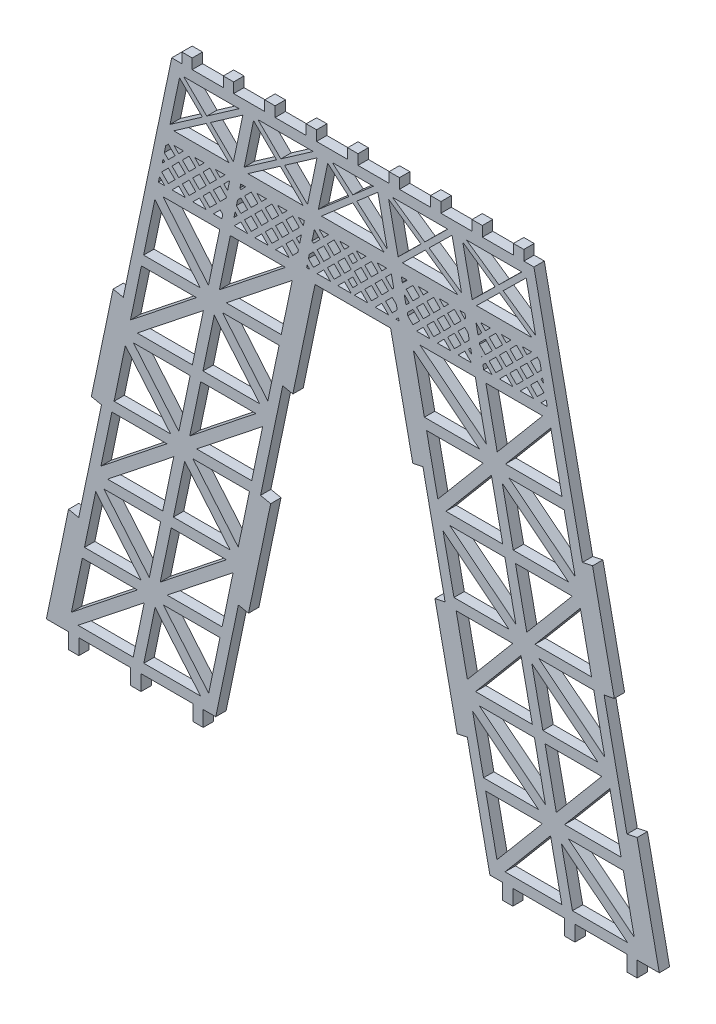
SolidWorks part; units mm, degrees
ref_plane "Front Plane" through (0, 0, 0) normal (0, 0, 1) x (1, 0, 0)
ref_plane "Top Plane" through (0, 0, 0) normal (0, 1, 0) x (1, 0, 0)
ref_plane "Right Plane" through (0, 0, 0) normal (1, 0, 0) x (0, 0, -1)
sketch "Sketch1" plane through (0, 0, 0) normal (0, 0, 1) x (1, 0, 0)
  line L1727 (344.6041, 258) -> (328.6274, 258)
  line L1728 (328.6274, 258) -> (347.7842, 242.7952)
  line L1729 (347.7842, 242.7952) -> (344.6041, 258)
  line L1730 (329.8663, 240.5406) -> (345.7992, 240.5406)
  line L1731 (345.7992, 240.5406) -> (326.6949, 255.7038)
  line L1732 (326.6949, 255.7038) -> (329.8663, 240.5406)
  line L1733 (354.4046, 237.5406) -> (370.3376, 237.5406)
  line L1734 (370.3376, 237.5406) -> (373.509, 222.3774)
  line L1735 (373.509, 222.3774) -> (354.4046, 237.5406)
  line L1736 (352.4197, 235.286) -> (355.5998, 220.0812)
  line L1737 (355.5998, 220.0812) -> (371.5764, 220.0812)
  line L1738 (371.5764, 220.0812) -> (352.4197, 235.286)
  line L1739 (353.1623, 217.0812) -> (337.1856, 217.0812)
  line L1740 (337.1856, 217.0812) -> (356.3424, 201.8765)
  line L1741 (356.3424, 201.8765) -> (353.1623, 217.0812)
  line L1742 (338.4245, 199.6218) -> (354.3574, 199.6218)
  line L1743 (354.3574, 199.6218) -> (335.2531, 214.785)
  line L1744 (335.2531, 214.785) -> (338.4245, 199.6218)
  line L1745 (362.9628, 196.6218) -> (378.8958, 196.6218)
  line L1746 (378.8958, 196.6218) -> (382.0672, 181.4586)
  line L1747 (382.0672, 181.4586) -> (362.9628, 196.6218)
  line L1748 (360.9779, 194.3672) -> (364.158, 179.1624)
  line L1749 (364.158, 179.1624) -> (380.1346, 179.1624)
  line L1750 (380.1346, 179.1624) -> (360.9779, 194.3672)
  line L1751 (361.7205, 176.1624) -> (345.7438, 176.1624)
  line L1752 (345.7438, 176.1624) -> (364.9006, 160.9577)
  line L1753 (364.9006, 160.9577) -> (361.7205, 176.1624)
  line L1754 (346.9827, 158.703) -> (362.9157, 158.703)
  line L1755 (362.9157, 158.703) -> (343.8113, 173.8662)
  line L1756 (343.8113, 173.8662) -> (346.9827, 158.703)
  line L1757 (371.521, 155.703) -> (387.454, 155.703)
  line L1758 (387.454, 155.703) -> (390.6254, 140.5398)
  line L1759 (390.6254, 140.5398) -> (371.521, 155.703)
  line L1760 (369.5361, 153.4484) -> (372.7162, 138.2436)
  line L1761 (372.7162, 138.2436) -> (388.6929, 138.2436)
  line L1762 (388.6929, 138.2436) -> (369.5361, 153.4484)
  line L1763 (369.6513, 138.2436) -> (366.3812, 153.8788)
  line L1764 (366.3812, 153.8788) -> (353.2223, 138.2436)
  line L1765 (353.2223, 138.2436) -> (369.6513, 138.2436)
  line L1766 (363.9954, 155.703) -> (350.8716, 140.1094)
  line L1767 (350.8716, 140.1094) -> (347.6101, 155.703)
  line L1768 (347.6101, 155.703) -> (363.9954, 155.703)
  line L1769 (364.7854, 176.1624) -> (368.0555, 160.5272)
  line L1770 (368.0555, 160.5272) -> (381.2144, 176.1624)
  line L1771 (381.2144, 176.1624) -> (364.7854, 176.1624)
  line L1772 (370.4413, 158.703) -> (383.5651, 174.2966)
  line L1773 (383.5651, 174.2966) -> (386.8266, 158.703)
  line L1774 (386.8266, 158.703) -> (370.4413, 158.703)
  line L1775 (361.0931, 179.1624) -> (357.8229, 194.7976)
  line L1776 (357.8229, 194.7976) -> (344.6641, 179.1624)
  line L1777 (344.6641, 179.1624) -> (361.0931, 179.1624)
  line L1778 (355.4372, 196.6218) -> (339.0519, 196.6218)
  line L1779 (339.0519, 196.6218) -> (342.3133, 181.0282)
  line L1780 (342.3133, 181.0282) -> (355.4372, 196.6218)
  line L1781 (356.2272, 217.0812) -> (359.4973, 201.446)
  line L1782 (359.4973, 201.446) -> (372.6562, 217.0812)
  line L1783 (372.6562, 217.0812) -> (356.2272, 217.0812)
  line L1784 (361.8831, 199.6218) -> (375.0069, 215.2154)
  line L1785 (375.0069, 215.2154) -> (378.2684, 199.6218)
  line L1786 (378.2684, 199.6218) -> (361.8831, 199.6218)
  line L1787 (352.5348, 220.0812) -> (349.2647, 235.7164)
  line L1788 (349.2647, 235.7164) -> (336.1059, 220.0812)
  line L1789 (336.1059, 220.0812) -> (352.5348, 220.0812)
  line L1790 (346.879, 237.5406) -> (330.4937, 237.5406)
  line L1791 (330.4937, 237.5406) -> (333.7551, 221.947)
  line L1792 (333.7551, 221.947) -> (346.879, 237.5406)
  line L1793 (347.669, 258) -> (350.9391, 242.3648)
  line L1794 (350.9391, 242.3648) -> (364.0979, 258)
  line L1795 (364.0979, 258) -> (347.669, 258)
  line L1796 (353.3249, 240.5406) -> (366.4487, 256.1342)
  line L1797 (366.4487, 256.1342) -> (369.7101, 240.5406)
  line L1798 (369.7101, 240.5406) -> (353.3249, 240.5406)
  line L1799 (340.9768, 289.9971) -> (343.7077, 276.9397)
  line L1800 (343.7077, 276.9397) -> (350.3463, 283.4684)
  line L1801 (350.3463, 283.4684) -> (340.9768, 289.9971)
  line L1802 (352.6864, 283.666) -> (362.0559, 277.1373)
  line L1803 (362.0559, 277.1373) -> (359.3249, 290.1947)
  line L1804 (359.3249, 290.1947) -> (352.6864, 283.666)
  line L1805 (360.9678, 276.0672) -> (351.5983, 282.5959)
  line L1806 (351.5983, 282.5959) -> (344.9598, 276.0672)
  line L1807 (344.9598, 276.0672) -> (360.9678, 276.0672)
  line L1808 (342.0648, 291.0672) -> (351.4343, 284.5385)
  line L1809 (351.4343, 284.5385) -> (358.0728, 291.0672)
  line L1810 (358.0728, 291.0672) -> (342.0648, 291.0672)
  line L1811 (340.6015, 277.1373) -> (337.8705, 290.1947)
  line L1812 (337.8705, 290.1947) -> (331.232, 283.666)
  line L1813 (331.232, 283.666) -> (340.6015, 277.1373)
  line L1814 (339.5134, 276.0672) -> (330.144, 282.5959)
  line L1815 (330.144, 282.5959) -> (323.5054, 276.0672)
  line L1816 (323.5054, 276.0672) -> (339.5134, 276.0672)
  line L1817 (319.5224, 289.9971) -> (322.2534, 276.9397)
  line L1818 (322.2534, 276.9397) -> (328.8919, 283.4684)
  line L1819 (328.8919, 283.4684) -> (319.5224, 289.9971)
  line L1820 (320.6104, 291.0672) -> (329.9799, 284.5385)
  line L1821 (329.9799, 284.5385) -> (336.6184, 291.0672)
  line L1822 (336.6184, 291.0672) -> (320.6104, 291.0672)
  line L1823 (319.1174, 277.2791) -> (316.4094, 290.2271)
  line L1824 (316.4094, 290.2271) -> (310.2902, 284.9261)
  line L1825 (310.2902, 284.9261) -> (319.1174, 277.2791)
  line L1826 (316.1711, 272.4369) -> (317.5474, 271.0607)
  line L1827 (317.5474, 271.0607) -> (318.9237, 272.4369)
  line L1828 (318.9237, 272.4369) -> (316.1711, 272.4369)
  line L1829 (310.1711, 272.4369) -> (311.5474, 271.0607)
  line L1830 (311.5474, 271.0607) -> (312.9237, 272.4369)
  line L1831 (312.9237, 272.4369) -> (310.1711, 272.4369)
  line L1832 (309.6081, 267) -> (311.5474, 265.0607)
  line L1833 (311.5474, 265.0607) -> (313.4868, 267)
  line L1834 (313.4868, 267) -> (311.5474, 268.9393)
  line L1835 (311.5474, 268.9393) -> (309.6081, 267)
  line L1836 (314.5474, 268.0607) -> (316.4868, 270)
  line L1837 (316.4868, 270) -> (314.5474, 271.9393)
  line L1838 (314.5474, 271.9393) -> (312.6081, 270)
  line L1839 (312.6081, 270) -> (314.5474, 268.0607)
  line L1840 (311.5474, 262.9393) -> (309.6081, 261)
  line L1841 (309.6081, 261) -> (313.4868, 261)
  line L1842 (313.4868, 261) -> (311.5474, 262.9393)
  line L1843 (314.5474, 265.9393) -> (312.6081, 264)
  line L1844 (312.6081, 264) -> (314.5474, 262.0607)
  line L1845 (314.5474, 262.0607) -> (316.4868, 264)
  line L1846 (316.4868, 264) -> (314.5474, 265.9393)
  line L1847 (317.5474, 268.9393) -> (315.6081, 267)
  line L1848 (315.6081, 267) -> (317.5474, 265.0607)
  line L1849 (317.5474, 265.0607) -> (319.4868, 267)
  line L1850 (319.4868, 267) -> (317.5474, 268.9393)
  line L1851 (323.1951, 272.4369) -> (323.4659, 271.1422)
  line L1852 (323.4659, 271.1422) -> (323.5474, 271.0607)
  line L1853 (323.5474, 271.0607) -> (324.9237, 272.4369)
  line L1854 (324.9237, 272.4369) -> (323.1951, 272.4369)
  line L1855 (320.2884, 271.6803) -> (318.6081, 270)
  line L1856 (318.6081, 270) -> (320.5474, 268.0607)
  line L1857 (320.5474, 268.0607) -> (320.9593, 268.4726)
  line L1858 (320.9593, 268.4726) -> (320.2884, 271.6803)
  line L1859 (322.5222, 261) -> (322.3641, 261.756)
  line L1860 (322.3641, 261.756) -> (321.6081, 261)
  line L1861 (321.6081, 261) -> (322.5222, 261)
  line L1862 (317.5474, 262.9393) -> (315.6081, 261)
  line L1863 (315.6081, 261) -> (319.4868, 261)
  line L1864 (319.4868, 261) -> (317.5474, 262.9393)
  line L1865 (321.7382, 264.7485) -> (320.5474, 265.9393)
  line L1866 (320.5474, 265.9393) -> (318.6081, 264)
  line L1867 (318.6081, 264) -> (320.5474, 262.0607)
  line L1868 (320.5474, 262.0607) -> (321.9972, 263.5104)
  line L1869 (321.9972, 263.5104) -> (321.7382, 264.7485)
  line L1870 (324.0269, 268.4598) -> (324.5319, 266.0452)
  line L1871 (324.5319, 266.0452) -> (325.4868, 267)
  line L1872 (325.4868, 267) -> (324.0269, 268.4598)
  line L1873 (326.5474, 271.9393) -> (324.6081, 270)
  line L1874 (324.6081, 270) -> (326.5474, 268.0607)
  line L1875 (326.5474, 268.0607) -> (328.4868, 270)
  line L1876 (328.4868, 270) -> (326.5474, 271.9393)
  line L1877 (328.1711, 272.4369) -> (329.5474, 271.0607)
  line L1878 (329.5474, 271.0607) -> (330.9237, 272.4369)
  line L1879 (330.9237, 272.4369) -> (328.1711, 272.4369)
  line L1880 (326.5474, 265.9393) -> (324.8989, 264.2908)
  line L1881 (324.8989, 264.2908) -> (325.0527, 263.5554)
  line L1882 (325.0527, 263.5554) -> (326.5474, 262.0607)
  line L1883 (326.5474, 262.0607) -> (328.4868, 264)
  line L1884 (328.4868, 264) -> (326.5474, 265.9393)
  line L1885 (329.5474, 268.9393) -> (327.6081, 267)
  line L1886 (327.6081, 267) -> (329.5474, 265.0607)
  line L1887 (329.5474, 265.0607) -> (331.4868, 267)
  line L1888 (331.4868, 267) -> (329.5474, 268.9393)
  line L1889 (332.5474, 271.9393) -> (330.6081, 270)
  line L1890 (330.6081, 270) -> (332.5474, 268.0607)
  line L1891 (332.5474, 268.0607) -> (334.4868, 270)
  line L1892 (334.4868, 270) -> (332.5474, 271.9393)
  line L1893 (334.1711, 272.4369) -> (335.5474, 271.0607)
  line L1894 (335.5474, 271.0607) -> (336.9237, 272.4369)
  line L1895 (336.9237, 272.4369) -> (334.1711, 272.4369)
  line L1896 (329.5474, 262.9393) -> (327.6081, 261)
  line L1897 (327.6081, 261) -> (331.4868, 261)
  line L1898 (331.4868, 261) -> (329.5474, 262.9393)
  line L1899 (332.5474, 265.9393) -> (330.6081, 264)
  line L1900 (330.6081, 264) -> (332.5474, 262.0607)
  line L1901 (332.5474, 262.0607) -> (334.4868, 264)
  line L1902 (334.4868, 264) -> (332.5474, 265.9393)
  line L1903 (335.5474, 268.9393) -> (333.6081, 267)
  line L1904 (333.6081, 267) -> (335.5474, 265.0607)
  line L1905 (335.5474, 265.0607) -> (337.4868, 267)
  line L1906 (337.4868, 267) -> (335.5474, 268.9393)
  line L1907 (338.5474, 271.9393) -> (336.6081, 270)
  line L1908 (336.6081, 270) -> (338.5474, 268.0607)
  line L1909 (338.5474, 268.0607) -> (340.4868, 270)
  line L1910 (340.4868, 270) -> (338.5474, 271.9393)
  line L1911 (341.5846, 272.4369) -> (340.1711, 272.4369)
  line L1912 (340.1711, 272.4369) -> (341.5474, 271.0607)
  line L1913 (341.5474, 271.0607) -> (341.8162, 271.3295)
  line L1914 (341.8162, 271.3295) -> (341.5846, 272.4369)
  line L1915 (343.5452, 263.0629) -> (343.221, 264.6129)
  line L1916 (343.221, 264.6129) -> (342.6081, 264)
  line L1917 (342.6081, 264) -> (343.5452, 263.0629)
  line L1918 (335.5474, 262.9393) -> (333.6081, 261)
  line L1919 (333.6081, 261) -> (337.4868, 261)
  line L1920 (337.4868, 261) -> (335.5474, 262.9393)
  line L1921 (338.5474, 265.9393) -> (336.6081, 264)
  line L1922 (336.6081, 264) -> (338.5474, 262.0607)
  line L1923 (338.5474, 262.0607) -> (340.4868, 264)
  line L1924 (340.4868, 264) -> (338.5474, 265.9393)
  line L1925 (342.5194, 267.9674) -> (341.5474, 268.9393)
  line L1926 (341.5474, 268.9393) -> (339.6081, 267)
  line L1927 (339.6081, 267) -> (341.5474, 265.0607)
  line L1928 (341.5474, 265.0607) -> (342.8541, 266.3673)
  line L1929 (342.8541, 266.3673) -> (342.5194, 267.9674)
  line L1930 (344.8081, 271.6787) -> (345.3888, 268.9021)
  line L1931 (345.3888, 268.9021) -> (346.4868, 270)
  line L1932 (346.4868, 270) -> (344.8081, 271.6787)
  line L1933 (346.1711, 272.4369) -> (347.5474, 271.0607)
  line L1934 (347.5474, 271.0607) -> (348.9237, 272.4369)
  line L1935 (348.9237, 272.4369) -> (346.1711, 272.4369)
  line L1936 (341.5474, 262.9393) -> (339.6081, 261)
  line L1937 (339.6081, 261) -> (343.4868, 261)
  line L1938 (343.4868, 261) -> (341.5474, 262.9393)
  line L1939 (346.3949, 264.0919) -> (346.4267, 263.9399)
  line L1940 (346.4267, 263.9399) -> (346.4868, 264)
  line L1941 (346.4868, 264) -> (346.3949, 264.0919)
  line L1942 (347.5474, 268.9393) -> (345.7558, 267.1477)
  line L1943 (345.7558, 267.1477) -> (345.8339, 266.7742)
  line L1944 (345.8339, 266.7742) -> (347.5474, 265.0607)
  line L1945 (347.5474, 265.0607) -> (349.4868, 267)
  line L1946 (349.4868, 267) -> (347.5474, 268.9393)
  line L1947 (350.5474, 271.9393) -> (348.6081, 270)
  line L1948 (348.6081, 270) -> (350.5474, 268.0607)
  line L1949 (350.5474, 268.0607) -> (352.4868, 270)
  line L1950 (352.4868, 270) -> (350.5474, 271.9393)
  line L1951 (352.1711, 272.4369) -> (353.5474, 271.0607)
  line L1952 (353.5474, 271.0607) -> (354.9237, 272.4369)
  line L1953 (354.9237, 272.4369) -> (352.1711, 272.4369)
  line L1954 (347.5474, 262.9393) -> (346.7936, 262.1855)
  line L1955 (346.7936, 262.1855) -> (347.0415, 261)
  line L1956 (347.0415, 261) -> (349.4868, 261)
  line L1957 (349.4868, 261) -> (347.5474, 262.9393)
  line L1958 (350.5474, 265.9393) -> (348.6081, 264)
  line L1959 (348.6081, 264) -> (350.5474, 262.0607)
  line L1960 (350.5474, 262.0607) -> (352.4868, 264)
  line L1961 (352.4868, 264) -> (350.5474, 265.9393)
  line L1962 (353.5474, 268.9393) -> (351.6081, 267)
  line L1963 (351.6081, 267) -> (353.5474, 265.0607)
  line L1964 (353.5474, 265.0607) -> (355.4868, 267)
  line L1965 (355.4868, 267) -> (353.5474, 268.9393)
  line L1966 (356.5474, 271.9393) -> (354.6081, 270)
  line L1967 (354.6081, 270) -> (356.5474, 268.0607)
  line L1968 (356.5474, 268.0607) -> (358.4868, 270)
  line L1969 (358.4868, 270) -> (356.5474, 271.9393)
  line L1970 (358.1711, 272.4369) -> (359.5474, 271.0607)
  line L1971 (359.5474, 271.0607) -> (360.9237, 272.4369)
  line L1972 (360.9237, 272.4369) -> (358.1711, 272.4369)
  line L1973 (353.5474, 262.9393) -> (351.6081, 261)
  line L1974 (351.6081, 261) -> (355.4868, 261)
  line L1975 (355.4868, 261) -> (353.5474, 262.9393)
  line L1976 (356.5474, 265.9393) -> (354.6081, 264)
  line L1977 (354.6081, 264) -> (356.5474, 262.0607)
  line L1978 (356.5474, 262.0607) -> (358.4868, 264)
  line L1979 (358.4868, 264) -> (356.5474, 265.9393)
  line L1980 (359.5474, 268.9393) -> (357.6081, 267)
  line L1981 (357.6081, 267) -> (359.5474, 265.0607)
  line L1982 (359.5474, 265.0607) -> (361.4868, 267)
  line L1983 (361.4868, 267) -> (359.5474, 268.9393)
  line L1984 (363.3006, 271.1862) -> (362.5474, 271.9393)
  line L1985 (362.5474, 271.9393) -> (360.6081, 270)
  line L1986 (360.6081, 270) -> (362.5474, 268.0607)
  line L1987 (362.5474, 268.0607) -> (363.7109, 269.2242)
  line L1988 (363.7109, 269.2242) -> (363.3006, 271.1862)
  line L1989 (363.6081, 267) -> (364.3263, 266.2817)
  line L1990 (364.3263, 266.2817) -> (364.0779, 267.4698)
  line L1991 (364.0779, 267.4698) -> (363.6081, 267)
  line L1992 (359.5474, 262.9393) -> (357.6081, 261)
  line L1993 (357.6081, 261) -> (361.4868, 261)
  line L1994 (361.4868, 261) -> (359.5474, 262.9393)
  line L1995 (362.5474, 265.9393) -> (360.6081, 264)
  line L1996 (360.6081, 264) -> (362.5474, 262.0607)
  line L1997 (362.5474, 262.0607) -> (364.4868, 264)
  line L1998 (364.4868, 264) -> (362.5474, 265.9393)
  line L1999 (365.1157, 262.5076) -> (365.431, 261)
  line L2000 (365.431, 261) -> (363.6081, 261)
  line L2001 (363.6081, 261) -> (365.1157, 262.5076)
  line L2002 (273.6855, 258) -> (289.6622, 258)
  line L2003 (289.6622, 258) -> (270.5055, 242.7952)
  line L2004 (270.5055, 242.7952) -> (273.6855, 258)
  line L2005 (288.4234, 240.5406) -> (272.4904, 240.5406)
  line L2006 (272.4904, 240.5406) -> (291.5948, 255.7038)
  line L2007 (291.5948, 255.7038) -> (288.4234, 240.5406)
  line L2008 (244.7807, 222.3774) -> (247.952, 237.5406)
  line L2009 (247.952, 237.5406) -> (263.885, 237.5406)
  line L2010 (263.885, 237.5406) -> (244.7807, 222.3774)
  line L2011 (265.87, 235.286) -> (262.6899, 220.0812)
  line L2012 (262.6899, 220.0812) -> (246.7132, 220.0812)
  line L2013 (246.7132, 220.0812) -> (265.87, 235.286)
  line L2014 (265.1273, 217.0812) -> (281.104, 217.0812)
  line L2015 (281.104, 217.0812) -> (261.9472, 201.8765)
  line L2016 (261.9472, 201.8765) -> (265.1273, 217.0812)
  line L2017 (279.8652, 199.6218) -> (263.9322, 199.6218)
  line L2018 (263.9322, 199.6218) -> (283.0366, 214.785)
  line L2019 (283.0366, 214.785) -> (279.8652, 199.6218)
  line L2020 (236.2224, 181.4586) -> (239.3938, 196.6218)
  line L2021 (239.3938, 196.6218) -> (255.3268, 196.6218)
  line L2022 (255.3268, 196.6218) -> (236.2224, 181.4586)
  line L2023 (257.3118, 194.3672) -> (254.1317, 179.1624)
  line L2024 (254.1317, 179.1624) -> (238.155, 179.1624)
  line L2025 (238.155, 179.1624) -> (257.3118, 194.3672)
  line L2026 (256.5691, 176.1624) -> (272.5458, 176.1624)
  line L2027 (272.5458, 176.1624) -> (253.389, 160.9577)
  line L2028 (253.389, 160.9577) -> (256.5691, 176.1624)
  line L2029 (271.307, 158.703) -> (255.374, 158.703)
  line L2030 (255.374, 158.703) -> (274.4783, 173.8662)
  line L2031 (274.4783, 173.8662) -> (271.307, 158.703)
  line L2032 (227.6642, 140.5398) -> (230.8356, 155.703)
  line L2033 (230.8356, 155.703) -> (246.7686, 155.703)
  line L2034 (246.7686, 155.703) -> (227.6642, 140.5398)
  line L2035 (229.5968, 138.2436) -> (245.5734, 138.2436)
  line L2036 (245.5734, 138.2436) -> (248.7535, 153.4484)
  line L2037 (248.7535, 153.4484) -> (229.5968, 138.2436)
  line L2038 (248.6384, 138.2436) -> (251.9085, 153.8788)
  line L2039 (251.9085, 153.8788) -> (265.0673, 138.2436)
  line L2040 (265.0673, 138.2436) -> (248.6384, 138.2436)
  line L2041 (270.6795, 155.703) -> (267.4181, 140.1094)
  line L2042 (267.4181, 140.1094) -> (254.2943, 155.703)
  line L2043 (254.2943, 155.703) -> (270.6795, 155.703)
  line L2044 (253.5042, 176.1624) -> (250.2341, 160.5272)
  line L2045 (250.2341, 160.5272) -> (237.0753, 176.1624)
  line L2046 (237.0753, 176.1624) -> (253.5042, 176.1624)
  line L2047 (231.4631, 158.703) -> (234.7245, 174.2966)
  line L2048 (234.7245, 174.2966) -> (247.8483, 158.703)
  line L2049 (247.8483, 158.703) -> (231.4631, 158.703)
  line L2050 (257.1966, 179.1624) -> (260.4667, 194.7976)
  line L2051 (260.4667, 194.7976) -> (273.6255, 179.1624)
  line L2052 (273.6255, 179.1624) -> (257.1966, 179.1624)
  line L2053 (275.9763, 181.0282) -> (279.2377, 196.6218)
  line L2054 (279.2377, 196.6218) -> (262.8525, 196.6218)
  line L2055 (262.8525, 196.6218) -> (275.9763, 181.0282)
  line L2056 (262.0624, 217.0812) -> (258.7923, 201.446)
  line L2057 (258.7923, 201.446) -> (245.6335, 217.0812)
  line L2058 (245.6335, 217.0812) -> (262.0624, 217.0812)
  line L2059 (240.0213, 199.6218) -> (243.2827, 215.2154)
  line L2060 (243.2827, 215.2154) -> (256.4065, 199.6218)
  line L2061 (256.4065, 199.6218) -> (240.0213, 199.6218)
  line L2062 (265.7548, 220.0812) -> (269.0249, 235.7164)
  line L2063 (269.0249, 235.7164) -> (282.1837, 220.0812)
  line L2064 (282.1837, 220.0812) -> (265.7548, 220.0812)
  line L2065 (284.5345, 221.947) -> (287.7959, 237.5406)
  line L2066 (287.7959, 237.5406) -> (271.4107, 237.5406)
  line L2067 (271.4107, 237.5406) -> (284.5345, 221.947)
  line L2068 (270.6206, 258) -> (267.3505, 242.3648)
  line L2069 (267.3505, 242.3648) -> (254.1917, 258)
  line L2070 (254.1917, 258) -> (270.6206, 258)
  line L2071 (248.5795, 240.5406) -> (251.8409, 256.1342)
  line L2072 (251.8409, 256.1342) -> (264.9647, 240.5406)
  line L2073 (264.9647, 240.5406) -> (248.5795, 240.5406)
  line L2074 (277.3129, 289.9971) -> (274.5819, 276.9397)
  line L2075 (274.5819, 276.9397) -> (267.9434, 283.4684)
  line L2076 (267.9434, 283.4684) -> (277.3129, 289.9971)
  line L2077 (258.9647, 290.1947) -> (256.2337, 277.1373)
  line L2078 (256.2337, 277.1373) -> (265.6032, 283.666)
  line L2079 (265.6032, 283.666) -> (258.9647, 290.1947)
  line L2080 (257.3218, 276.0672) -> (266.6913, 282.5959)
  line L2081 (266.6913, 282.5959) -> (273.3298, 276.0672)
  line L2082 (273.3298, 276.0672) -> (257.3218, 276.0672)
  line L2083 (276.2248, 291.0672) -> (266.8553, 284.5385)
  line L2084 (266.8553, 284.5385) -> (260.2168, 291.0672)
  line L2085 (260.2168, 291.0672) -> (276.2248, 291.0672)
  line L2086 (277.6881, 277.1373) -> (280.4191, 290.1947)
  line L2087 (280.4191, 290.1947) -> (287.0576, 283.666)
  line L2088 (287.0576, 283.666) -> (277.6881, 277.1373)
  line L2089 (278.7762, 276.0672) -> (288.1457, 282.5959)
  line L2090 (288.1457, 282.5959) -> (294.7842, 276.0672)
  line L2091 (294.7842, 276.0672) -> (278.7762, 276.0672)
  line L2092 (298.7673, 289.9971) -> (296.0363, 276.9397)
  line L2093 (296.0363, 276.9397) -> (289.3978, 283.4684)
  line L2094 (289.3978, 283.4684) -> (298.7673, 289.9971)
  line L2095 (297.6792, 291.0672) -> (288.3097, 284.5385)
  line L2096 (288.3097, 284.5385) -> (281.6712, 291.0672)
  line L2097 (281.6712, 291.0672) -> (297.6792, 291.0672)
  line L2098 (299.1722, 277.2791) -> (301.8803, 290.2271)
  line L2099 (301.8803, 290.2271) -> (307.9994, 284.9261)
  line L2100 (307.9994, 284.9261) -> (299.1722, 277.2791)
  line L2101 (302.1185, 272.4369) -> (300.7422, 271.0607)
  line L2102 (300.7422, 271.0607) -> (299.3659, 272.4369)
  line L2103 (299.3659, 272.4369) -> (302.1185, 272.4369)
  line L2104 (308.1185, 272.4369) -> (306.7422, 271.0607)
  line L2105 (306.7422, 271.0607) -> (305.3659, 272.4369)
  line L2106 (305.3659, 272.4369) -> (308.1185, 272.4369)
  line L2107 (308.6816, 267) -> (306.7422, 265.0607)
  line L2108 (306.7422, 265.0607) -> (304.8029, 267)
  line L2109 (304.8029, 267) -> (306.7422, 268.9393)
  line L2110 (306.7422, 268.9393) -> (308.6816, 267)
  line L2111 (303.7422, 268.0607) -> (301.8029, 270)
  line L2112 (301.8029, 270) -> (303.7422, 271.9393)
  line L2113 (303.7422, 271.9393) -> (305.6816, 270)
  line L2114 (305.6816, 270) -> (303.7422, 268.0607)
  line L2115 (304.8029, 261) -> (308.6816, 261)
  line L2116 (308.6816, 261) -> (306.7422, 262.9393)
  line L2117 (306.7422, 262.9393) -> (304.8029, 261)
  line L2118 (303.7422, 265.9393) -> (305.6816, 264)
  line L2119 (305.6816, 264) -> (303.7422, 262.0607)
  line L2120 (303.7422, 262.0607) -> (301.8029, 264)
  line L2121 (301.8029, 264) -> (303.7422, 265.9393)
  line L2122 (300.7422, 268.9393) -> (302.6816, 267)
  line L2123 (302.6816, 267) -> (300.7422, 265.0607)
  line L2124 (300.7422, 265.0607) -> (298.8029, 267)
  line L2125 (298.8029, 267) -> (300.7422, 268.9393)
  line L2126 (295.0945, 272.4369) -> (294.8237, 271.1422)
  line L2127 (294.8237, 271.1422) -> (294.7422, 271.0607)
  line L2128 (294.7422, 271.0607) -> (293.3659, 272.4369)
  line L2129 (293.3659, 272.4369) -> (295.0945, 272.4369)
  line L2130 (298.0012, 271.6803) -> (299.6816, 270)
  line L2131 (299.6816, 270) -> (297.7422, 268.0607)
  line L2132 (297.7422, 268.0607) -> (297.3303, 268.4726)
  line L2133 (297.3303, 268.4726) -> (298.0012, 271.6803)
  line L2134 (295.7674, 261) -> (295.9255, 261.756)
  line L2135 (295.9255, 261.756) -> (296.6816, 261)
  line L2136 (296.6816, 261) -> (295.7674, 261)
  line L2137 (298.8029, 261) -> (302.6816, 261)
  line L2138 (302.6816, 261) -> (300.7422, 262.9393)
  line L2139 (300.7422, 262.9393) -> (298.8029, 261)
  line L2140 (296.5514, 264.7485) -> (297.7422, 265.9393)
  line L2141 (297.7422, 265.9393) -> (299.6816, 264)
  line L2142 (299.6816, 264) -> (297.7422, 262.0607)
  line L2143 (297.7422, 262.0607) -> (296.2925, 263.5104)
  line L2144 (296.2925, 263.5104) -> (296.5514, 264.7485)
  line L2145 (294.2627, 268.4598) -> (293.7577, 266.0452)
  line L2146 (293.7577, 266.0452) -> (292.8029, 267)
  line L2147 (292.8029, 267) -> (294.2627, 268.4598)
  line L2148 (291.7422, 271.9393) -> (293.6816, 270)
  line L2149 (293.6816, 270) -> (291.7422, 268.0607)
  line L2150 (291.7422, 268.0607) -> (289.8029, 270)
  line L2151 (289.8029, 270) -> (291.7422, 271.9393)
  line L2152 (290.1185, 272.4369) -> (288.7422, 271.0607)
  line L2153 (288.7422, 271.0607) -> (287.3659, 272.4369)
  line L2154 (287.3659, 272.4369) -> (290.1185, 272.4369)
  line L2155 (291.7422, 265.9393) -> (293.3908, 264.2908)
  line L2156 (293.3908, 264.2908) -> (293.237, 263.5554)
  line L2157 (293.237, 263.5554) -> (291.7422, 262.0607)
  line L2158 (291.7422, 262.0607) -> (289.8029, 264)
  line L2159 (289.8029, 264) -> (291.7422, 265.9393)
  line L2160 (288.7422, 268.9393) -> (290.6816, 267)
  line L2161 (290.6816, 267) -> (288.7422, 265.0607)
  line L2162 (288.7422, 265.0607) -> (286.8029, 267)
  line L2163 (286.8029, 267) -> (288.7422, 268.9393)
  line L2164 (285.7422, 271.9393) -> (287.6816, 270)
  line L2165 (287.6816, 270) -> (285.7422, 268.0607)
  line L2166 (285.7422, 268.0607) -> (283.8029, 270)
  line L2167 (283.8029, 270) -> (285.7422, 271.9393)
  line L2168 (284.1185, 272.4369) -> (282.7422, 271.0607)
  line L2169 (282.7422, 271.0607) -> (281.3659, 272.4369)
  line L2170 (281.3659, 272.4369) -> (284.1185, 272.4369)
  line L2171 (286.8029, 261) -> (290.6816, 261)
  line L2172 (290.6816, 261) -> (288.7422, 262.9393)
  line L2173 (288.7422, 262.9393) -> (286.8029, 261)
  line L2174 (285.7422, 265.9393) -> (287.6816, 264)
  line L2175 (287.6816, 264) -> (285.7422, 262.0607)
  line L2176 (285.7422, 262.0607) -> (283.8029, 264)
  line L2177 (283.8029, 264) -> (285.7422, 265.9393)
  line L2178 (282.7422, 268.9393) -> (284.6816, 267)
  line L2179 (284.6816, 267) -> (282.7422, 265.0607)
  line L2180 (282.7422, 265.0607) -> (280.8029, 267)
  line L2181 (280.8029, 267) -> (282.7422, 268.9393)
  line L2182 (279.7422, 271.9393) -> (281.6816, 270)
  line L2183 (281.6816, 270) -> (279.7422, 268.0607)
  line L2184 (279.7422, 268.0607) -> (277.8029, 270)
  line L2185 (277.8029, 270) -> (279.7422, 271.9393)
  line L2186 (276.7051, 272.4369) -> (278.1185, 272.4369)
  line L2187 (278.1185, 272.4369) -> (276.7422, 271.0607)
  line L2188 (276.7422, 271.0607) -> (276.4734, 271.3295)
  line L2189 (276.4734, 271.3295) -> (276.7051, 272.4369)
  line L2190 (274.7445, 263.0629) -> (275.0686, 264.6129)
  line L2191 (275.0686, 264.6129) -> (275.6816, 264)
  line L2192 (275.6816, 264) -> (274.7445, 263.0629)
  line L2193 (280.8029, 261) -> (284.6816, 261)
  line L2194 (284.6816, 261) -> (282.7422, 262.9393)
  line L2195 (282.7422, 262.9393) -> (280.8029, 261)
  line L2196 (279.7422, 265.9393) -> (281.6816, 264)
  line L2197 (281.6816, 264) -> (279.7422, 262.0607)
  line L2198 (279.7422, 262.0607) -> (277.8029, 264)
  line L2199 (277.8029, 264) -> (279.7422, 265.9393)
  line L2200 (275.7702, 267.9674) -> (276.7422, 268.9393)
  line L2201 (276.7422, 268.9393) -> (278.6816, 267)
  line L2202 (278.6816, 267) -> (276.7422, 265.0607)
  line L2203 (276.7422, 265.0607) -> (275.4356, 266.3673)
  line L2204 (275.4356, 266.3673) -> (275.7702, 267.9674)
  line L2205 (273.4815, 271.6787) -> (272.9008, 268.9021)
  line L2206 (272.9008, 268.9021) -> (271.8029, 270)
  line L2207 (271.8029, 270) -> (273.4815, 271.6787)
  line L2208 (272.1185, 272.4369) -> (270.7422, 271.0607)
  line L2209 (270.7422, 271.0607) -> (269.3659, 272.4369)
  line L2210 (269.3659, 272.4369) -> (272.1185, 272.4369)
  line L2211 (274.8029, 261) -> (278.6816, 261)
  line L2212 (278.6816, 261) -> (276.7422, 262.9393)
  line L2213 (276.7422, 262.9393) -> (274.8029, 261)
  line L2214 (271.8948, 264.0919) -> (271.863, 263.9399)
  line L2215 (271.863, 263.9399) -> (271.8029, 264)
  line L2216 (271.8029, 264) -> (271.8948, 264.0919)
  line L2217 (270.7422, 268.9393) -> (272.5339, 267.1477)
  line L2218 (272.5339, 267.1477) -> (272.4558, 266.7742)
  line L2219 (272.4558, 266.7742) -> (270.7422, 265.0607)
  line L2220 (270.7422, 265.0607) -> (268.8029, 267)
  line L2221 (268.8029, 267) -> (270.7422, 268.9393)
  line L2222 (267.7422, 271.9393) -> (269.6816, 270)
  line L2223 (269.6816, 270) -> (267.7422, 268.0607)
  line L2224 (267.7422, 268.0607) -> (265.8029, 270)
  line L2225 (265.8029, 270) -> (267.7422, 271.9393)
  line L2226 (266.1185, 272.4369) -> (264.7422, 271.0607)
  line L2227 (264.7422, 271.0607) -> (263.3659, 272.4369)
  line L2228 (263.3659, 272.4369) -> (266.1185, 272.4369)
  line L2229 (268.8029, 261) -> (271.2481, 261)
  line L2230 (271.2481, 261) -> (271.496, 262.1855)
  line L2231 (271.496, 262.1855) -> (270.7422, 262.9393)
  line L2232 (270.7422, 262.9393) -> (268.8029, 261)
  line L2233 (267.7422, 265.9393) -> (269.6816, 264)
  line L2234 (269.6816, 264) -> (267.7422, 262.0607)
  line L2235 (267.7422, 262.0607) -> (265.8029, 264)
  line L2236 (265.8029, 264) -> (267.7422, 265.9393)
  line L2237 (264.7422, 268.9393) -> (266.6816, 267)
  line L2238 (266.6816, 267) -> (264.7422, 265.0607)
  line L2239 (264.7422, 265.0607) -> (262.8029, 267)
  line L2240 (262.8029, 267) -> (264.7422, 268.9393)
  line L2241 (261.7422, 271.9393) -> (263.6816, 270)
  line L2242 (263.6816, 270) -> (261.7422, 268.0607)
  line L2243 (261.7422, 268.0607) -> (259.8029, 270)
  line L2244 (259.8029, 270) -> (261.7422, 271.9393)
  line L2245 (260.1185, 272.4369) -> (258.7422, 271.0607)
  line L2246 (258.7422, 271.0607) -> (257.3659, 272.4369)
  line L2247 (257.3659, 272.4369) -> (260.1185, 272.4369)
  line L2248 (262.8029, 261) -> (266.6816, 261)
  line L2249 (266.6816, 261) -> (264.7422, 262.9393)
  line L2250 (264.7422, 262.9393) -> (262.8029, 261)
  line L2251 (261.7422, 265.9393) -> (263.6816, 264)
  line L2252 (263.6816, 264) -> (261.7422, 262.0607)
  line L2253 (261.7422, 262.0607) -> (259.8029, 264)
  line L2254 (259.8029, 264) -> (261.7422, 265.9393)
  line L2255 (258.7422, 268.9393) -> (260.6816, 267)
  line L2256 (260.6816, 267) -> (258.7422, 265.0607)
  line L2257 (258.7422, 265.0607) -> (256.8029, 267)
  line L2258 (256.8029, 267) -> (258.7422, 268.9393)
  line L2259 (254.9891, 271.1862) -> (255.7422, 271.9393)
  line L2260 (255.7422, 271.9393) -> (257.6816, 270)
  line L2261 (257.6816, 270) -> (255.7422, 268.0607)
  line L2262 (255.7422, 268.0607) -> (254.5787, 269.2242)
  line L2263 (254.5787, 269.2242) -> (254.9891, 271.1862)
  line L2264 (254.2118, 267.4698) -> (253.9633, 266.2817)
  line L2265 (253.9633, 266.2817) -> (254.6816, 267)
  line L2266 (254.6816, 267) -> (254.2118, 267.4698)
  line L2267 (256.8029, 261) -> (260.6816, 261)
  line L2268 (260.6816, 261) -> (258.7422, 262.9393)
  line L2269 (258.7422, 262.9393) -> (256.8029, 261)
  line L2270 (255.7422, 265.9393) -> (257.6816, 264)
  line L2271 (257.6816, 264) -> (255.7422, 262.0607)
  line L2272 (255.7422, 262.0607) -> (253.8029, 264)
  line L2273 (253.8029, 264) -> (255.7422, 265.9393)
  line L2274 (253.1739, 262.5076) -> (252.8586, 261)
  line L2275 (252.8586, 261) -> (254.6816, 261)
  line L2276 (254.6816, 261) -> (253.1739, 262.5076)
  line L2277 (309.1448, 262.6581) -> (310.4868, 264)
  line L2278 (310.4868, 264) -> (309.1448, 265.3419)
  line L2279 (309.1448, 265.3419) -> (307.8029, 264)
  line L2280 (307.8029, 264) -> (309.1448, 262.6581)
  line L2281 (309.1448, 283.9338) -> (318.2255, 276.0672)
  line L2282 (318.2255, 276.0672) -> (300.0642, 276.0672)
  line L2283 (300.0642, 276.0672) -> (309.1448, 283.9338)
  line L2284 (315.0882, 291.0672) -> (309.1448, 285.9184)
  line L2285 (309.1448, 285.9184) -> (303.2014, 291.0672)
  line L2286 (303.2014, 291.0672) -> (315.0882, 291.0672)
  line L2287 (309.1448, 271.3419) -> (310.4868, 270)
  line L2288 (310.4868, 270) -> (309.1448, 268.6581)
  line L2289 (309.1448, 268.6581) -> (307.8029, 270)
  line L2290 (307.8029, 270) -> (309.1448, 271.3419)
  line L2291 (358.6448, 294.0672) -> (358.6448, 297)
  line L2292 (358.6448, 297) -> (355.6448, 297)
  line L2293 (355.6448, 297) -> (355.6448, 294.0672)
  line L2294 (355.6448, 294.0672) -> (346.6448, 294.0672)
  line L2295 (346.6448, 294.0672) -> (346.6448, 297)
  line L2296 (346.6448, 297) -> (343.6448, 297)
  line L2297 (343.6448, 297) -> (343.6448, 294.0672)
  line L2298 (343.6448, 294.0672) -> (334.6448, 294.0672)
  line L2299 (334.6448, 294.0672) -> (334.6448, 297)
  line L2300 (334.6448, 297) -> (331.6448, 297)
  line L2301 (331.6448, 297) -> (331.6448, 294.0672)
  line L2302 (331.6448, 294.0672) -> (322.6448, 294.0672)
  line L2303 (322.6448, 294.0672) -> (322.6448, 297)
  line L2304 (322.6448, 297) -> (319.6448, 297)
  line L2305 (319.6448, 297) -> (319.6448, 294.0672)
  line L2306 (319.6448, 294.0672) -> (310.6448, 294.0672)
  line L2307 (310.6448, 294.0672) -> (310.6448, 297)
  line L2308 (310.6448, 297) -> (307.6448, 297)
  line L2309 (307.6448, 297) -> (307.6448, 294.0672)
  line L2310 (307.6448, 294.0672) -> (298.6448, 294.0672)
  line L2311 (298.6448, 294.0672) -> (298.6448, 297)
  line L2312 (298.6448, 297) -> (295.6448, 297)
  line L2313 (295.6448, 297) -> (295.6448, 294.0672)
  line L2314 (295.6448, 294.0672) -> (286.6448, 294.0672)
  line L2315 (286.6448, 294.0672) -> (286.6448, 297)
  line L2316 (286.6448, 297) -> (283.6448, 297)
  line L2317 (283.6448, 297) -> (283.6448, 294.0672)
  line L2318 (283.6448, 294.0672) -> (274.6448, 294.0672)
  line L2319 (274.6448, 294.0672) -> (274.6448, 297)
  line L2320 (274.6448, 297) -> (271.6448, 297)
  line L2321 (271.6448, 297) -> (271.6448, 294.0672)
  line L2322 (271.6448, 294.0672) -> (262.6448, 294.0672)
  line L2323 (262.6448, 294.0672) -> (262.6448, 297)
  line L2324 (262.6448, 297) -> (259.6448, 297)
  line L2325 (259.6448, 297) -> (259.6448, 294.0672)
  line L2326 (259.6448, 294.0672) -> (256.7097, 294.0672)
  line L2327 (256.7097, 294.0672) -> (242.6842, 227.008)
  line L2328 (242.6842, 227.008) -> (239.7478, 227.6222)
  line L2329 (239.7478, 227.6222) -> (233.4526, 197.5234)
  line L2330 (233.4526, 197.5234) -> (236.389, 196.9093)
  line L2331 (236.389, 196.9093) -> (229.7868, 165.3423)
  line L2332 (229.7868, 165.3423) -> (226.8503, 165.9565)
  line L2333 (226.8503, 165.9565) -> (220.4267, 135.2436)
  line L2334 (220.4267, 135.2436) -> (226.8392, 135.2436)
  line L2335 (226.8392, 135.2436) -> (226.8392, 130.7436)
  line L2336 (226.8392, 130.7436) -> (229.8392, 130.7436)
  line L2337 (229.8392, 130.7436) -> (229.8392, 135.2436)
  line L2338 (229.8392, 135.2436) -> (244.8392, 135.2436)
  line L2339 (244.8392, 135.2436) -> (244.8392, 130.7436)
  line L2340 (244.8392, 130.7436) -> (247.8392, 130.7436)
  line L2341 (247.8392, 130.7436) -> (247.8392, 135.2436)
  line L2342 (247.8392, 135.2436) -> (262.8392, 135.2436)
  line L2343 (262.8392, 135.2436) -> (262.8392, 130.7436)
  line L2344 (262.8392, 130.7436) -> (265.8392, 130.7436)
  line L2345 (265.8392, 130.7436) -> (265.8392, 135.2436)
  line L2346 (265.8392, 135.2436) -> (269.4653, 135.2436)
  line L2347 (269.4653, 135.2436) -> (276.0124, 166.5469)
  line L2348 (276.0124, 166.5469) -> (278.9489, 165.9327)
  line L2349 (278.9489, 165.9327) -> (285.3675, 196.6218)
  line L2350 (285.3675, 196.6218) -> (282.4311, 197.236)
  line L2351 (282.4311, 197.236) -> (288.8497, 227.9251)
  line L2352 (288.8497, 227.9251) -> (291.7862, 227.3109)
  line L2353 (291.7862, 227.3109) -> (298.2049, 258)
  line L2354 (298.2049, 258) -> (320.0848, 258)
  line L2355 (320.0848, 258) -> (326.5034, 227.3109)
  line L2356 (326.5034, 227.3109) -> (329.4399, 227.9251)
  line L2357 (329.4399, 227.9251) -> (335.8586, 197.236)
  line L2358 (335.8586, 197.236) -> (332.9221, 196.6218)
  line L2359 (332.9221, 196.6218) -> (339.3408, 165.9327)
  line L2360 (339.3408, 165.9327) -> (342.2772, 166.5469)
  line L2361 (342.2772, 166.5469) -> (348.8243, 135.2436)
  line L2362 (348.8243, 135.2436) -> (352.4505, 135.2436)
  line L2363 (352.4505, 135.2436) -> (352.4505, 130.7436)
  line L2364 (352.4505, 130.7436) -> (355.4505, 130.7436)
  line L2365 (355.4505, 130.7436) -> (355.4505, 135.2436)
  line L2366 (355.4505, 135.2436) -> (370.4505, 135.2436)
  line L2367 (370.4505, 135.2436) -> (370.4505, 130.7436)
  line L2368 (370.4505, 130.7436) -> (373.4505, 130.7436)
  line L2369 (373.4505, 130.7436) -> (373.4505, 135.2436)
  line L2370 (373.4505, 135.2436) -> (388.4505, 135.2436)
  line L2371 (388.4505, 135.2436) -> (388.4505, 130.7436)
  line L2372 (388.4505, 130.7436) -> (391.4505, 130.7436)
  line L2373 (391.4505, 130.7436) -> (391.4505, 135.2436)
  line L2374 (391.4505, 135.2436) -> (397.863, 135.2436)
  line L2375 (397.863, 135.2436) -> (391.4393, 165.9565)
  line L2376 (391.4393, 165.9565) -> (388.5029, 165.3423)
  line L2377 (388.5029, 165.3423) -> (381.9006, 196.9093)
  line L2378 (381.9006, 196.9093) -> (384.8371, 197.5234)
  line L2379 (384.8371, 197.5234) -> (378.5419, 227.6222)
  line L2380 (378.5419, 227.6222) -> (375.6054, 227.008)
  line L2381 (375.6054, 227.008) -> (361.5799, 294.0672)
  line L2382 (361.5799, 294.0672) -> (358.6448, 294.0672)
extrude "Boss-Extrude1" add sketch "Sketch1" along normal blind 3 contours L2381 L2382 L2291 L2292 L2293 L2294 L2295 L2296 L2297 L2298 L2299 L2300 L2301 L2302 L2303 L2304 L2305 L2306 L2307 L2308 L2309 L2310 L2311 L2312 L2313 L2314 L2315 L2316 L2317 L2318 L2319 L2320 L2321 L2322 L2323 L2324 L2325 L2326 L2327 L2328 L2329 L2330 L2331 L2332 L2333 L2334 L2335 L2336 L2337 L2338 L2339 region at (360.1124, 291.6356, 0)
